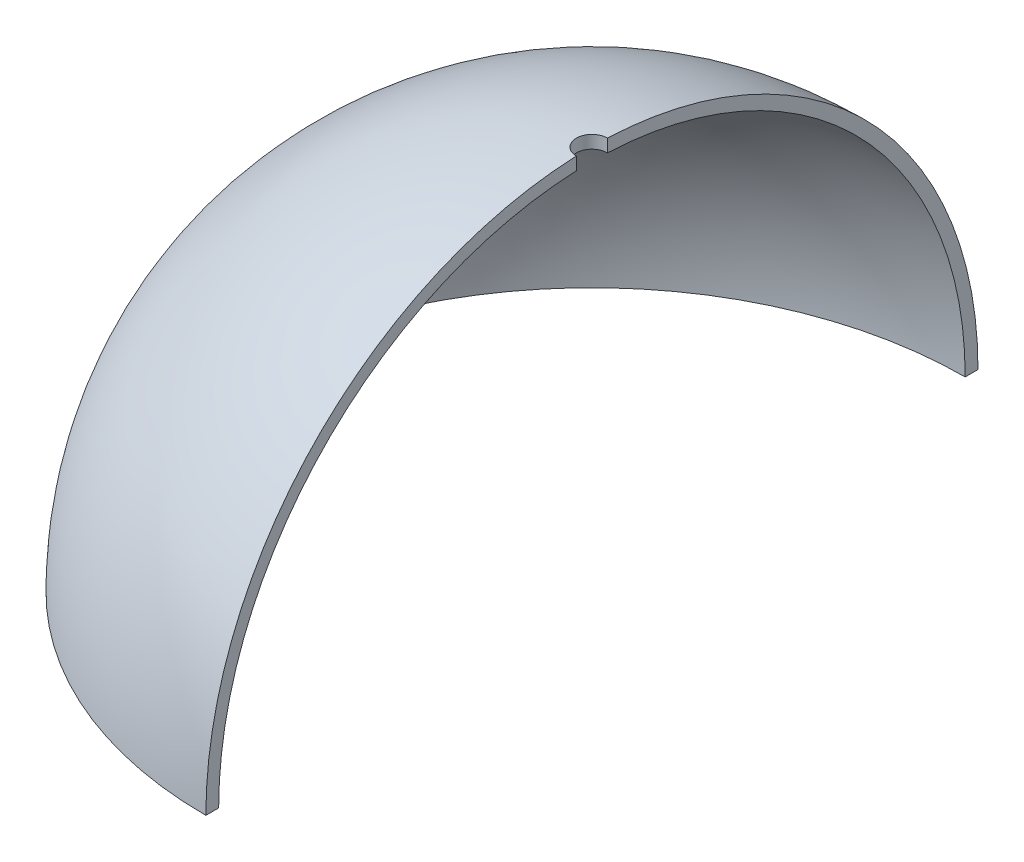
SolidWorks part; units mm, degrees
ref_plane "Front" through (0, 0, 0) normal (0, 0, 1) x (1, 0, 0)
ref_plane "Top" through (0, 0, 0) normal (0, 1, 0) x (1, 0, 0)
ref_plane "Right" through (0, 0, 0) normal (1, 0, 0) x (0, 0, -1)
sketch "Sketch2" plane through (0, 0, 0) normal (0, 1, 0) x (1, 0, 0)
  line L0 (0, -9945) -> (0, -9615)
  line L1 (0, 9615) -> (0, 9945)
  line L2 (0, -3077.1526) -> (0, 2858.4717) construction
  line L3 (0, -55) -> (0, 55) construction
  arc A0 (0, 9615) -> (0, -9615) centre (0, 0) ccw
  arc A1 (0, 9945) -> (0, -9945) centre (0, 0) ccw
  dimension "D1" = 330
revolve "Revolve1" add sketch "Sketch2" angle 90 about L2
sketch "Sketch5" plane through (0, 0, 0) normal (0, 1, 0) x (1, 0, 0)
  circle A0 centre (0, 0) radius 400
  dimension "D1" = 800
extrude "Cut-Extrude1" cut sketch "Sketch5" along normal blind 10987 contours A0
